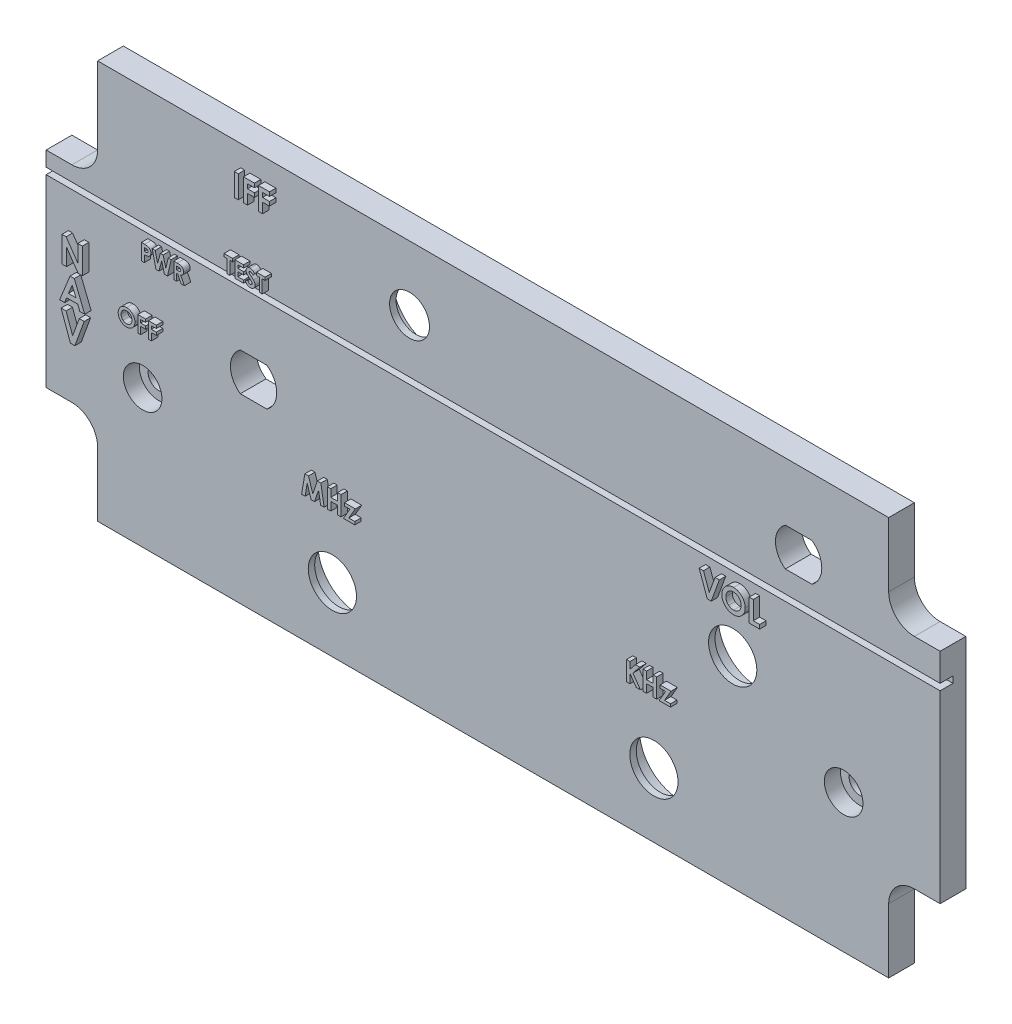
SolidWorks part; units mm, degrees
ref_plane "Front Plane" through (0, 0, 0) normal (0, 0, 1) x (1, 0, 0)
ref_plane "Top Plane" through (0, 0, 0) normal (0, 1, 0) x (1, 0, 0)
ref_plane "Right Plane" through (0, 0, 0) normal (1, 0, 0) x (0, 0, -1)
sketch "Sketch1" plane through (0, 0, 0) normal (0, 0, 1) x (1, 0, 0)
  line L0 (39.5, 10) -> (99.5, 10) construction
  line L1 (8, 0) -> (131, 0)
  line L2 (0, 14) -> (0, 46)
  line L3 (8, 62) -> (131, 62)
  line L4 (139, 14) -> (139, 48)
  line L5 (69.5, 62) -> (69.5, 0) construction
  line L13 (8, 62) -> (8, 50)
  line L14 (4, 46) -> (0, 46)
  line L15 (8, 0) -> (8, 10)
  line L16 (4, 14) -> (0, 14)
  line L17 (131, 62) -> (131, 52)
  line L18 (135, 48) -> (139, 48)
  line L19 (131, 0) -> (131, 10)
  line L20 (135, 14) -> (139, 14)
  line L21 (0, 30) -> (139, 30) construction
  line L22 (0, 0) -> (131, 0) construction
  line L23 (0, 0) -> (0, 64.6609) construction
  line L31 (30.1866, 28.2676) -> (34.3134, 28.2676) construction
  line L32 (34.3134, 34.1676) -> (30.1866, 34.1676) construction
  line L33 (30.1866, 28.2676) -> (34.3134, 28.2676)
  line L34 (34.3134, 34.1676) -> (30.1866, 34.1676)
  line L39 (114.9366, 47.05) -> (119.0634, 47.05)
  line L40 (119.0634, 52.95) -> (114.9366, 52.95)
  line L41 (114.9366, 47.05) -> (119.0634, 47.05)
  line L42 (119.0634, 52.95) -> (114.9366, 52.95)
  arc A8 (8, 10) -> (4, 14) centre (4, 10) ccw
  arc A9 (8, 50) -> (4, 46) centre (4, 50) cw
  arc A11 (131, 10) -> (135, 14) centre (135, 10) cw
  arc A12 (131, 52) -> (135, 48) centre (135, 52) ccw
  circle A15 centre (44.5, 10) radius 3.75 construction
  circle A16 centre (94.5, 10) radius 3.75 construction
  circle A17 centre (106.75, 31.2176) radius 3.75 construction
  circle A18 centre (15, 21.5) radius 1.65 construction
  circle A19 centre (124, 21.5) radius 1.65 construction
  circle A20 centre (15, 21.5) radius 1.65
  circle A21 centre (124, 21.5) radius 1.65
  circle A22 centre (106.75, 31.2176) radius 3.75
  circle A23 centre (94.5, 10) radius 3.75
  circle A24 centre (44.5, 10) radius 3.75
  circle A27 centre (56.5, 52) radius 3.1 construction
  circle A29 centre (56.5, 52) radius 3.1
  arc A43 (34.3134, 28.2676) -> (34.3134, 34.1676) centre (32.25, 31.2176) ccw construction
  arc A44 (30.1866, 34.1676) -> (30.1866, 28.2676) centre (32.25, 31.2176) ccw construction
  arc A45 (34.3134, 28.2676) -> (34.3134, 34.1676) centre (32.25, 31.2176) ccw
  arc A46 (30.1866, 34.1676) -> (30.1866, 28.2676) centre (32.25, 31.2176) ccw
  arc A51 (119.0634, 47.05) -> (119.0634, 52.95) centre (117, 50) ccw
  arc A52 (114.9366, 52.95) -> (114.9366, 47.05) centre (117, 50) ccw
  arc A53 (119.0634, 47.05) -> (119.0634, 52.95) centre (117, 50) ccw
  arc A54 (114.9366, 52.95) -> (114.9366, 47.05) centre (117, 50) ccw
  point P13 (69.5, 10)
  point P21 (131, 14)
  point P25 (8, 46)
  point P40 (131, 48)
  point P55 (2, 46)
  dimension "D3" = 30
  dimension "D4" = 14
  dimension "D5" = 16
  dimension "D8" = 4
  dimension "D12" = 4
  dimension "D13" = 0
  dimension "D6" = 60
  dimension "D7" = 10
  dimension "D11" = 8
  dimension "D15" = 123
  dimension "D16" = 139
  dimension "D20" = 62
  dimension "D22" = 8
  dimension "D9" = 8
  dimension "D10" = 14
extrude "Boss-Extrude1" add sketch "Sketch1" along normal blind 4
sketch "Sketch2" plane through (0, 0, 0) normal (0, 0, -1) x (-1, 0, 0)
  line L0 (-119.0634, 52.95) -> (-114.9366, 52.95) construction
  line L1 (-114.9366, 47.05) -> (-119.0634, 47.05) construction
  line L24 (-4, 16) -> (-2, 16)
  line L25 (-2, 16) -> (-2, 44)
  line L26 (-2, 44) -> (-4, 44)
  line L27 (-10, 50) -> (-10, 60)
  line L28 (-10, 60) -> (-129, 60)
  line L29 (-129, 60) -> (-129, 52)
  line L30 (-135, 46) -> (-137, 46)
  line L31 (-137, 46) -> (-137, 16)
  line L32 (-137, 16) -> (-135, 16)
  line L33 (-129, 10) -> (-129, 2)
  line L34 (-129, 2) -> (-10, 2)
  line L35 (-10, 2) -> (-10, 10)
  line L36 (-4, 16) -> (-2, 16)
  line L37 (-2, 16) -> (-2, 44)
  line L38 (-2, 44) -> (-4, 44)
  line L39 (-10, 50) -> (-10, 60)
  line L40 (-10, 60) -> (-129, 60)
  line L41 (-129, 60) -> (-129, 52)
  line L42 (-135, 46) -> (-137, 46)
  line L43 (-137, 46) -> (-137, 16)
  line L44 (-137, 16) -> (-135, 16)
  line L45 (-129, 10) -> (-129, 2)
  line L46 (-129, 2) -> (-10, 2)
  line L47 (-10, 2) -> (-10, 10)
  circle A5 centre (-44.5, 10) radius 3.75 construction
  circle A6 centre (-94.5, 10) radius 3.75 construction
  circle A7 centre (-106.75, 31.2176) radius 3.75 construction
  circle A9 centre (-44.5, 10) radius 3.75 construction
  circle A10 centre (-94.5, 10) radius 3.75 construction
  circle A11 centre (-106.75, 31.2176) radius 3.75 construction
  circle A13 centre (-44.5, 10) radius 6.25
  circle A14 centre (-94.5, 10) radius 6.25
  circle A15 centre (-106.75, 31.2176) radius 6.25
  arc A16 (-119.0634, 52.95) -> (-119.0634, 47.05) centre (-117, 50) ccw construction
  circle A18 centre (-56.5, 52) radius 3.1 construction
  circle A19 centre (-56.5, 52) radius 3.1 construction
  arc A20 (-114.9366, 47.05) -> (-114.9366, 52.95) centre (-117, 50) ccw construction
  arc A21 (-119.0634, 52.95) -> (-119.0634, 47.05) centre (-117, 50) ccw construction
  arc A22 (-114.9366, 47.05) -> (-114.9366, 52.95) centre (-117, 50) ccw construction
  arc A23 (-119.0634, 52.95) -> (-114.9366, 52.95) centre (-117, 50) cw construction
  circle A24 centre (-56.5, 52) radius 6.75
  arc A26 (-119.0634, 47.05) -> (-114.9366, 47.05) centre (-117, 50) ccw construction
  arc A27 (-120.439, 54.9167) -> (-113.561, 54.9167) centre (-117, 50) cw
  arc A28 (-4, 16) -> (-10, 10) centre (-4, 10) ccw
  arc A29 (-10, 50) -> (-4, 44) centre (-4, 50) ccw
  arc A30 (-135, 46) -> (-129, 52) centre (-135, 52) ccw
  arc A31 (-129, 10) -> (-135, 16) centre (-135, 10) ccw
  arc A32 (-4, 16) -> (-10, 10) centre (-4, 10) ccw
  arc A33 (-10, 50) -> (-4, 44) centre (-4, 50) ccw
  arc A34 (-135, 46) -> (-129, 52) centre (-135, 52) ccw
  arc A35 (-129, 10) -> (-135, 16) centre (-135, 10) ccw
  arc A36 (-120.439, 54.9167) -> (-120.439, 45.0833) centre (-117, 50) ccw
  arc A37 (-120.439, 45.0833) -> (-113.561, 45.0833) centre (-117, 50) ccw
  arc A38 (-113.561, 45.0833) -> (-113.561, 54.9167) centre (-117, 50) ccw
  arc A39 (-30.1866, 28.2676) -> (-30.1866, 34.1676) centre (-32.25, 31.2176) ccw construction
  circle A40 centre (-32.25, 31.2176) radius 3.6 construction
  circle A41 centre (-32.25, 31.2176) radius 6
  circle M33 centre (-106.75, 31.2176) radius 3.75
  circle M34 centre (-94.5, 10) radius 3.75
  circle M35 centre (-44.5, 10) radius 3.75
  circle M43 centre (-56.5, 52) radius 3.1
  dimension "D1" = 2.5
  dimension "D2" = 2.4
  dimension "D6" = 12
  dimension "D4" = 13.5
  dimension "D3" = 2
  dimension "D5" = 2.4
extrude "Back holes" cut sketch "Sketch2" against normal blind 3 contours A14 M34 | A15 M33 | A24 M43 | A13 M35 region at (50.5732, 10, 0) region at (100.5732, 10, 0) region at (112.8232, 31.2176, 0) region at (63.0591, 52, 0)
sketch "Sketch3" plane through (0, 0, 4) normal (0, 0, 1) x (1, 0, 0)
  circle A0 centre (124, 21.5) radius 1.65 construction
  circle A1 centre (15, 21.5) radius 1.65 construction
  circle A2 centre (124, 21.5) radius 1.65 construction
  circle A3 centre (15, 21.5) radius 1.65 construction
  circle A4 centre (15, 21.5) radius 3
  circle A5 centre (124, 21.5) radius 3
  dimension "D1" = 6
extrude "Cut-Extrude2" cut sketch "Sketch3" against normal blind 2.5
sketch "Sketch5" plane through (0, 0, 4) normal (0, 0, 1) x (1, 0, 0)
  line L0 (139, 42.6747) -> (0, 42.6747)
  line L1 (139, 14) -> (139, 48) construction
  line L2 (0, 46) -> (0, 14) construction
  line L3 (0, 42.6747) -> (0, 43.6747)
  line L4 (0, 43.6747) -> (139, 43.6747)
  line L5 (139, 43.6747) -> (139, 42.6747)
  dimension "D1" = 1
extrude "Cut-Extrude3" cut sketch "Sketch5" against normal blind 2
sketch "Sketch4" plane through (0, 0, 4) normal (0, 0, 1) x (1, 0, 0)
  line L0 (6.5219, 26.9631) -> (6.5219, 14.5758) construction
  line L2 (33.1689, 20.5068) -> (113.2155, 20.5068) construction
  line L3 (-3.8412, 32.8725) -> (13.9628, 32.8725) construction
  line L4 (-4.2039, 27.8725) -> (13.9628, 27.8725) construction
  line L5 (-4.2039, 22.8725) -> (13.9628, 22.8725) construction
  line L6 (3.5219, 33.1522) -> (3.5219, -6.8271) construction
  text T0 "N" font "Century Gothic" height 4
  text T1 "<b>OFF</b>" font "Century Gothic" height 2.5
  text T2 "<b>PWR</b>" font "Century Gothic" height 2.5
  text T3 "<b>TEST</b>" font "Century Gothic" height 2.5
  text T4 "<b>VOL</b>" font "Century Gothic" height 3.5
  text T5 "MHz" font "Century Gothic" height 3
  text T6 "KHz" font "Century Gothic" height 3
  text T7 "A" font "Century Gothic" height 4
  text T8 "V" font "Century Gothic" height 4
  text T9 "IFF" font "Century Gothic" height 3.5
  dimension "D1" = 5
  dimension "D2" = 5
  dimension "D3" = 3
extrude "Textos" add sketch "Sketch4" along normal blind 1
